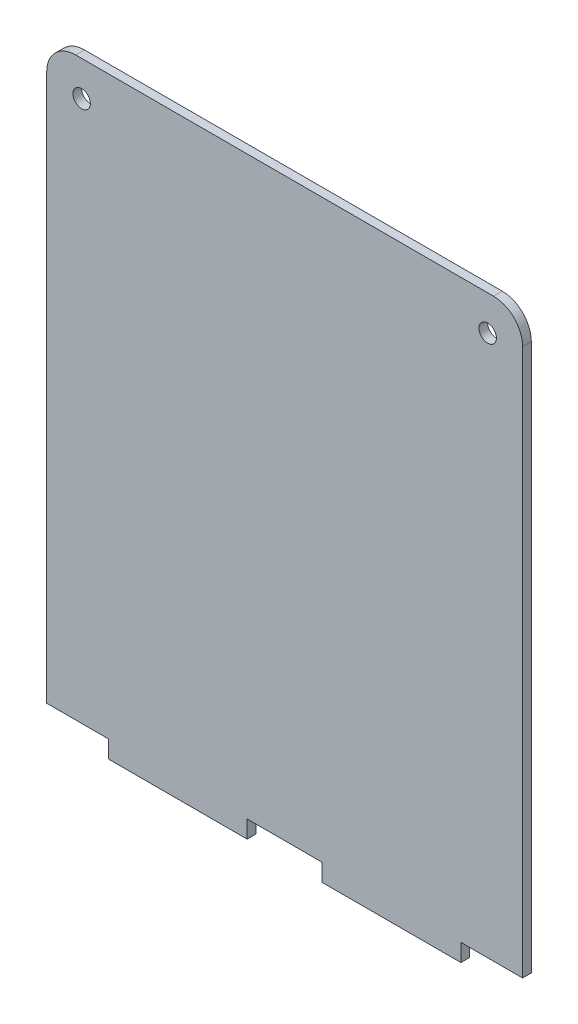
SolidWorks part; units mm, degrees
ref_plane "Front Plane" through (0, 0, 0) normal (0, 0, 1) x (1, 0, 0)
ref_plane "Top Plane" through (0, 0, 0) normal (0, 1, 0) x (1, 0, 0)
ref_plane "Right Plane" through (0, 0, 0) normal (1, 0, 0) x (0, 0, -1)
sketch "Sketch1" plane through (0, 0, 0) normal (0, 0, 1) x (1, 0, 0)
  line L1 (0, 0) -> (81.8, 0)
  line L2 (0, 0) -> (0, 102)
  line L3 (0, 102) -> (81.8, 102)
  line L4 (81.8, 0) -> (81.8, 102)
  dimension "D1" = 81.8
  dimension "D2" = 102
extrude "Boss-Extrude1" add sketch "Sketch1" along normal blind 1.5
sketch "Sketch2" plane through (0, 0, 1.5) normal (0, 0, 1) x (1, 0, 0)
  line L0 (40.9, 102) -> (40.9, 0)
  line L1 (81.8, 102) -> (0, 102) construction
  line L2 (0, 0) -> (81.8, 0) construction
  line L3 (81.8, 0) -> (81.8, 3)
  line L4 (0, 0) -> (10.6, 0)
  line L5 (0, 0) -> (0, 3)
  line L6 (0, 3) -> (10.6, 3)
  line L7 (10.6, 0) -> (10.6, 3)
  line L8 (34.455, 0) -> (47.345, 0)
  line L9 (34.455, 0) -> (34.455, 3)
  line L10 (34.455, 3) -> (47.345, 3)
  line L11 (47.345, 0) -> (47.345, 3)
  line L12 (81.8, 0) -> (71.2, 0)
  line L13 (71.2, 0) -> (71.2, 3)
  line L14 (81.8, 3) -> (71.2, 3)
  line L15 (0, 102) -> (0, 0) construction
  circle A0 centre (6, 96) radius 1.5
  circle A1 centre (75.8, 96) radius 1.5
  line M8 (0, 102) -> (0, 0)
  line M9 (0, 0) -> (81.8, 0)
  line M10 (81.8, 0) -> (81.8, 102)
  dimension "D5" = 6
  dimension "D1" = 3
  dimension "D2" = 10.6
  dimension "D3" = 12.89
  dimension "D4" = 6.445
  dimension "D6" = 6
extrude "Cut-Extrude1" cut sketch "Sketch2" against normal through all contours L7 L6 M9 M8 | L11 L10 L0 M9 | L10 L9 L0 M9 | L14 L13 M10 M9 | A0 | A1 region at (44.1225, 1.5, 1.5) region at (37.6775, 1.5, 1.5) region at (76.5, 1.5, 1.5) region at (5.3, 1.5, 1.5)
sketch "Sketch3" plane through (0, 0, 1.5) normal (0, 0, 1) x (1, 0, 0)
  line L0 (0, 33.6536) -> (81.8, 33.6536)
  line L1 (0, 102) -> (0, 3) construction
  line L2 (81.8, 3) -> (81.8, 102) construction
  line L3 (40.9, 102) -> (40.9, 3)
  line L4 (81.8, 102) -> (0, 102) construction
  line L5 (34.455, 3) -> (47.345, 3) construction
  line L6 (35.4, 39.1536) -> (46.4, 39.1536)
  line L7 (35.4, 28.1536) -> (46.4, 28.1536)
  circle A0 centre (35.4, 33.6536) radius 5.5
  circle A1 centre (46.4, 33.6536) radius 5.5
  point P19 (40.9, 28.1536)
  point P20 (40.9, 39.1536)
  dimension "D1" = 5.5
  dimension "D2" = 11
  dimension "D3" = 68.3464
extrude "Cut-Extrude2" [suppressed] cut sketch "Sketch3" against normal through all contours L0 A0 | L0 A0 | A1 L0 | A1 L0 | A0 L7 L3 | L7 A1 L3 | L3 A1 L6 | A0 L3 L6
fillet "Fillet1" radius 5 2 edges at (81.8, 102, 0.75) (0, 102, 0.75)
